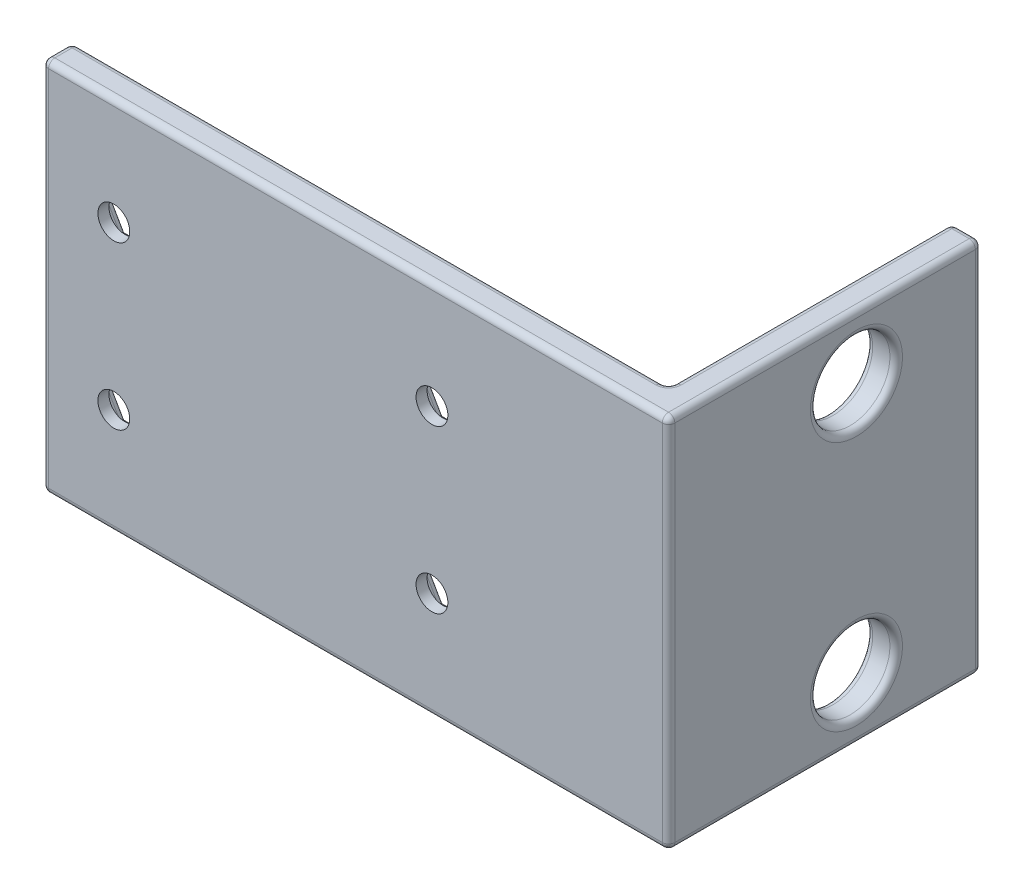
SolidWorks part; units mm, degrees
ref_plane "Front Plane" through (0, 0, 0) normal (0, 0, 1) x (1, 0, 0)
ref_plane "Top Plane" through (0, 0, 0) normal (0, 1, 0) x (1, 0, 0)
ref_plane "Right Plane" through (0, 0, 0) normal (1, 0, 0) x (0, 0, -1)
sketch "Sketch1" plane through (0, 0, 0) normal (0, 1, 0) x (1, 0, 0)
  line L0 (0, 0) -> (0, 22.6188)
  line L1 (0, 22.6188) -> (2.3813, 22.6188)
  line L2 (2.3813, 22.6188) -> (2.3813, -2.3812)
  line L3 (2.3813, -2.3812) -> (-47.6187, -2.3813)
  line L4 (-47.6187, -2.3813) -> (-47.6187, 0)
  line L5 (-47.6187, 0) -> (0, 0)
  dimension "D1" = 2.3813
  dimension "D2" = 25
  dimension "D3" = 50
extrude "Boss-Extrude1" add sketch "Sketch1" along normal blind 30
sketch "Sketch2" plane through (0, 0, 2.3812) normal (0, 0, 1) x (1, 0, 0)
  line L4 (-47.6187, 0) -> (2.3813, 0)
  line L5 (2.3813, 0) -> (2.3813, 30)
  line L6 (2.3813, 30) -> (-47.6187, 30)
  line L7 (-47.6187, 30) -> (-47.6187, 0)
  line L8 (-47.6187, 0) -> (2.3813, 0) construction
  line L9 (2.3813, 0) -> (2.3813, 30) construction
  line L10 (2.3813, 30) -> (-47.6187, 30) construction
  line L11 (-47.6187, 30) -> (-47.6187, 0) construction
  circle A0 centre (-41.91, 8.523) radius 1.27 construction
  circle A1 centre (-41.91, 8.523) radius 1.27
  circle A2 centre (-16.51, 8.523) radius 1.27 construction
  circle A3 centre (-16.51, 8.523) radius 1.27
  circle A4 centre (-16.51, 21.477) radius 1.27 construction
  circle A5 centre (-16.51, 21.477) radius 1.27
  circle A6 centre (-41.91, 21.477) radius 1.27 construction
  circle A7 centre (-41.91, 21.477) radius 1.27
  dimension "D1" = 0
extrude "Cut-Extrude1" cut sketch "Sketch2" against normal through all
sketch "Sketch3" plane through (2.3813, 0, 0) normal (1, 0, 0) x (0, 0, -1)
  line L4 (-2.3812, 0) -> (22.6188, 0)
  line L5 (22.6188, 0) -> (22.6188, 30)
  line L6 (22.6188, 30) -> (-2.3812, 30)
  line L7 (-2.3812, 30) -> (-2.3812, 0)
  line L8 (-2.3812, 0) -> (22.6188, 0) construction
  line L9 (22.6188, 0) -> (22.6188, 30) construction
  line L10 (22.6188, 30) -> (-2.3812, 30) construction
  line L11 (-2.3812, 30) -> (-2.3812, 0) construction
  circle A0 centre (12.6188, 25) radius 3.175
  circle A1 centre (12.6188, 5) radius 3.175
  point P2 (12.6188, 25)
  point P4 (12.6188, 5)
  dimension "D5" = 6.35
  dimension "D2" = 20
  dimension "D3" = 5
  dimension "D4" = 15
  dimension "D1" = 0
extrude "Cut-Extrude2" cut sketch "Sketch3" against normal through all
fillet "Fillet1" radius 0.5 26 edges at (-47.6187, 15, 2.3813) (-47.6187, 0, 1.1906) (-22.6187, 0, 2.3812) (2.3813, 15, 2.3812) (2.3813, 0, -10.1188) (2.3813, 5, -15.7938) (2.3813, 25, -15.7938) (2.3813, 15, -22.6188) (1.1906, 0, -22.6188) (1.1906, 30, -22.6188) (2.3813, 30, -10.1188) (-22.6187, 30, 2.3812) (-47.6187, 30, 1.1906) (0, 15, -22.6188) (0, 30, -11.3094) (0, 0, -11.3094) (0, 5, -15.7938) (0, 25, -15.7938) (0, 15, 0) (-23.8094, 30, 0) (-47.6187, 15, 0) (-23.8094, 0, 0) (-40.64, 8.523, 0) (-15.24, 8.523, 0) (-15.24, 21.477, 0) (-40.64, 21.477, 0)
sketch "Sketch5" plane through (0, 0, 0) normal (0, 0, -1) x (-1, 0, 0)
  line L1 (19.2813, 21.477) -> (17.8956, 23.877)
  line L2 (17.8956, 23.877) -> (15.1244, 23.877)
  line L3 (15.1244, 23.877) -> (13.7387, 21.477)
  line L4 (13.7387, 21.477) -> (15.1244, 19.077)
  line L5 (15.1244, 19.077) -> (17.8956, 19.077)
  line L6 (17.8956, 19.077) -> (19.2813, 21.477)
  line L7 (19.2813, 8.523) -> (17.8956, 10.923)
  line L8 (17.8956, 10.923) -> (15.1244, 10.923)
  line L9 (15.1244, 10.923) -> (13.7387, 8.523)
  line L10 (13.7387, 8.523) -> (15.1244, 6.123)
  line L11 (15.1244, 6.123) -> (17.8956, 6.123)
  line L12 (17.8956, 6.123) -> (19.2813, 8.523)
  line L13 (39.1387, 8.523) -> (40.5244, 6.123)
  line L14 (40.5244, 6.123) -> (43.2956, 6.123)
  line L15 (43.2956, 6.123) -> (44.6813, 8.523)
  line L16 (44.6813, 8.523) -> (43.2956, 10.923)
  line L17 (43.2956, 10.923) -> (40.5244, 10.923)
  line L18 (40.5244, 10.923) -> (39.1387, 8.523)
  line L19 (39.1387, 21.477) -> (40.5244, 19.077)
  line L20 (40.5244, 19.077) -> (43.2956, 19.077)
  line L21 (43.2956, 19.077) -> (44.6813, 21.477)
  line L22 (44.6813, 21.477) -> (43.2956, 23.877)
  line L23 (43.2956, 23.877) -> (40.5244, 23.877)
  line L24 (40.5244, 23.877) -> (39.1387, 21.477)
  circle A0 centre (16.51, 21.477) radius 2.4 construction
  circle A1 centre (16.51, 8.523) radius 2.4 construction
  circle A2 centre (41.91, 8.523) radius 2.4 construction
  circle A3 centre (41.91, 21.477) radius 2.4 construction
  dimension "D1" = 4.8
  dimension "D2" = 4.8
  dimension "D3" = 4.8
  dimension "D4" = 4.8
extrude "Cut-Extrude3" cut sketch "Sketch5" against normal blind 1.5
fillet "Fillet2" radius 0.5 24 edges at (-16.51, 23.877, 0) (-14.4315, 22.677, 0) (-14.4315, 20.277, 0) (-16.51, 19.077, 0) (-18.5885, 20.277, 0) (-18.5885, 22.677, 0) (-16.51, 10.923, 0) (-14.4315, 9.723, 0) (-14.4315, 7.323, 0) (-16.51, 6.123, 0) (-18.5885, 7.323, 0) (-18.5885, 9.723, 0) (-41.91, 6.123, 0) (-43.9885, 7.323, 0) (-43.9885, 9.723, 0) (-41.91, 10.923, 0) (-39.8315, 9.723, 0) (-39.8315, 7.323, 0) (-41.91, 19.077, 0) (-43.9885, 20.277, 0) (-43.9885, 22.677, 0) (-41.91, 23.877, 0) (-39.8315, 22.677, 0) (-39.8315, 20.277, 0)
